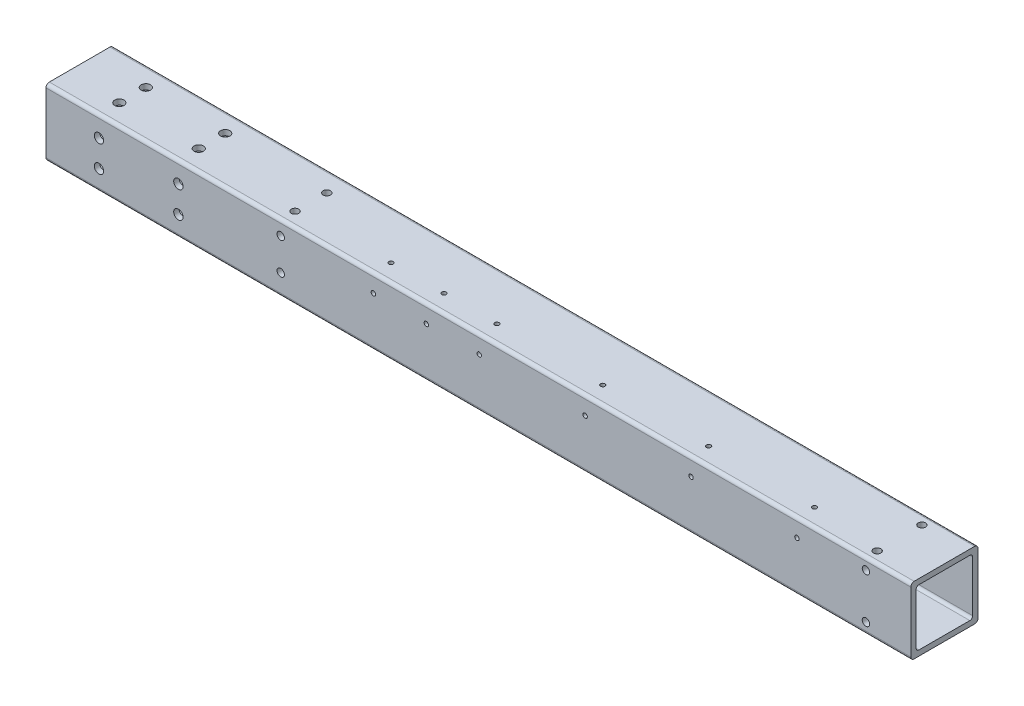
SolidWorks part; units mm, degrees
material "ASTM A36 Steel"
ref_plane "Front" through (0, 0, 0) normal (0, 0, 1) x (1, 0, 0)
ref_plane "Top" through (0, 0, 0) normal (0, 1, 0) x (1, 0, 0)
ref_plane "Right" through (0, 0, 0) normal (1, 0, 0) x (0, 0, -1)
sketch "Sketch1" plane through (0, 0, 0) normal (1, 0, 0) x (0, 0, -1)
  line L0 (-16.002, 0) -> (-19.05, 0) construction
  line L1 (17.145, -19.05) -> (-17.145, -19.05) construction
  line L2 (19.05, -17.145) -> (19.05, 17.145) construction
  line L3 (17.145, 19.05) -> (-17.145, 19.05) construction
  line L4 (-19.05, -17.145) -> (-19.05, 17.145) construction
  line L5 (19.05, -19.05) -> (-19.05, 19.05) construction
  line L6 (19.05, 19.05) -> (-19.05, -19.05) construction
  line L7 (14.4018, 16.002) -> (-14.4018, 16.002) construction
  line L8 (16.002, 14.4018) -> (16.002, -14.4018) construction
  line L9 (14.4018, -16.002) -> (-14.4018, -16.002) construction
  line L10 (-16.002, 14.4018) -> (-16.002, -14.4018) construction
  line L11 (16.002, 16.002) -> (-16.002, -16.002) construction
  line L12 (16.002, -16.002) -> (-16.002, 16.002) construction
  line L13 (0, -16.002) -> (0, -19.05) construction
  line L14 (16.002, -14.4018) -> (16.002, -19.05) construction
  line L15 (16.002, 0) -> (19.05, 0) construction
  line L16 (16.002, -19.05) -> (19.05, -19.05) construction
  arc A0 (-14.4018, -16.002) -> (-16.002, -14.4018) centre (-14.4018, -14.4018) cw construction
  arc A1 (16.002, -14.4018) -> (14.4018, -16.002) centre (14.4018, -14.4018) cw construction
  arc A2 (14.4018, 16.002) -> (16.002, 14.4018) centre (14.4018, 14.4018) cw construction
  arc A3 (-14.4018, 16.002) -> (-16.002, 14.4018) centre (-14.4018, 14.4018) ccw construction
  arc A4 (17.145, -19.05) -> (19.05, -17.145) centre (17.145, -17.145) ccw construction
  arc A5 (19.05, 17.145) -> (17.145, 19.05) centre (17.145, 17.145) ccw construction
  arc A6 (-17.145, 19.05) -> (-19.05, 17.145) centre (-17.145, 17.145) ccw construction
  arc A7 (-17.145, -19.05) -> (-19.05, -17.145) centre (-17.145, -17.145) cw construction
  point P0 (0, 0)
  point P6 (0, 0)
  dimension "D2" = 1.6002
  dimension "D3" = 1.905
  dimension "Outside Width" = 38.1
  dimension "Ouside Height" = 38.1
  dimension "Inside Height" = 32.004
  dimension "Wall Thickness" = 3.048
sketch "Sketch2" plane through (0, 0, 0) normal (0, 0, 1) x (1, 0, 0)
  line L0 (-245, 0) -> (245, 0) construction
  point P3 (-209.948, 0)
  point P4 (209.948, 0)
  dimension "Length" = 490
  dimension "D1" = 35.052
  dimension "D2" = 35.052
sketch "Sketch4" plane through (0, 0, 0) normal (1, 0, 0) x (0, 0, -1)
  line L8 (19.05, -17.145) -> (19.05, 17.145)
  line L9 (17.145, 19.05) -> (-17.145, 19.05)
  line L10 (-19.05, -17.145) -> (-19.05, 17.145)
  line L11 (17.145, -19.05) -> (-17.145, -19.05)
  line L12 (16.002, 14.4018) -> (16.002, -14.4018)
  line L13 (14.4018, -16.002) -> (-14.4018, -16.002)
  line L14 (-16.002, 14.4018) -> (-16.002, -14.4018)
  line L15 (14.4018, 16.002) -> (-14.4018, 16.002)
  arc A8 (19.05, 17.145) -> (17.145, 19.05) centre (17.145, 17.145) ccw
  arc A9 (-17.145, 19.05) -> (-19.05, 17.145) centre (-17.145, 17.145) ccw
  arc A10 (-19.05, -17.145) -> (-17.145, -19.05) centre (-17.145, -17.145) ccw
  arc A11 (17.145, -19.05) -> (19.05, -17.145) centre (17.145, -17.145) ccw
  arc A12 (14.4018, -16.002) -> (16.002, -14.4018) centre (14.4018, -14.4018) ccw
  arc A13 (-16.002, -14.4018) -> (-14.4018, -16.002) centre (-14.4018, -14.4018) ccw
  arc A14 (-14.4018, 16.002) -> (-16.002, 14.4018) centre (-14.4018, 14.4018) ccw
  arc A15 (16.002, 14.4018) -> (14.4018, 16.002) centre (14.4018, 14.4018) ccw
extrude "Boss-Extrude1" add sketch "Sketch4" along normal up to vertex (-245 mm away) and the other way up to vertex (-245 mm away) up to point (-245, 0, 0) other way up to point (245, 0, 0)
hole_wizard "Tap Drill for M5x0.8 Tap1" positions "Sketch5" profile "Sketch6" hole size "M5x0.8" standard "ANSI Metric" end condition up to next
sketch "Sketch5" plane through (0, 19.05, 0) normal (0, 1, 0) x (1, 0, 0)
  line L0 (-112, -10.95) -> (-112, 7.05) construction
  line L2 (-245, 17.145) -> (-245, -17.145) construction
  line L3 (245, 19.05) -> (-245, 19.05) construction
  point P0 (-112, 7.05)
  point P2 (-112, -10.95)
  point P20 (-112, -1.95)
  dimension "D1" = 18
  dimension "D2" = 133
  dimension "D3" = 21
sketch "Sketch6" plane through (-112, 19.05, -7.05) normal (1, 0, 0) x (0, 0, 1)
  line L0 (0, 0) -> (0, 3.048)
  line L1 (0, 3.048) -> (2.1, 3.048)
  line L2 (2.1, 3.048) -> (2.1, 0)
  line L5 (2.1, 0) -> (0, 0)
  line L11 (0, -6.35) -> (0, 107.95) construction
  dimension "Thru Hole Dia." = 4.2
  dimension "Thru Hole Depth" = 3.048
ref_plane "Plane1" through (0, 0, 0) normal (0, -0.7071, 0.7071) x (1, 0, 0)
hole_wizard "Tap Drill for M3x0.5 Tap1" positions "Sketch8" profile "Sketch9" hole size "M3x0.5" standard "ANSI Metric" end condition up to next
sketch "Sketch8" plane through (0, 0, 19.05) normal (0, 0, 1) x (1, 0, 0)
  line L0 (245, 17.145) -> (245, -17.145) construction
  line L1 (245, 19.05) -> (-245, 19.05) construction
  line L3 (-59.5, 9.05) -> (0.5, 9.05) construction
  point P0 (180.5, 9.05)
  point P5 (120.5, 9.05)
  point P6 (60.5, 9.05)
  point P7 (0.5, 9.05)
  point P8 (-59.5, 9.05)
  point P27 (-29.5, 9.05)
  dimension "D2" = 60
  dimension "D3" = 64.5
  dimension "D4" = 10
  dimension "D1" = 5
sketch "Sketch9" plane through (180.5, 9.05, 19.05) normal (1, 0, 0) x (0, -1, 0)
  line L0 (0, 0) -> (0, 3.048)
  line L1 (0, 3.048) -> (1.25, 3.048)
  line L2 (1.25, 3.048) -> (1.25, 0)
  line L5 (1.25, 0) -> (0, 0)
  line L11 (0, -6.35) -> (0, 107.95) construction
  dimension "Thru Hole Dia." = 2.5
  dimension "Thru Hole Depth" = 3.048
hole_wizard "Tap Drill for M5x0.8 Tap2" positions "Sketch21" profile "Sketch22" hole size "M5x0.8" standard "ANSI Metric"
sketch "Sketch21" plane through (0, 0, 19.05) normal (0, 0, 1) x (1, 0, 0)
  line L0 (219.6, 12.7) -> (219.6, -12.7) construction
  line L2 (245, 17.145) -> (245, -17.145) construction
  point P0 (219.6, 12.7)
  point P2 (219.6, -12.7)
  point P11 (245, 0)
  point P12 (219.6, 0)
  dimension "D1" = 25.4
  dimension "D2" = 25.4
sketch "Sketch22" plane through (219.6, 12.7, 19.05) normal (1, 0, 0) x (0, -1, 0)
  line L0 (0, 0) -> (0, 6.2618)
  line L1 (0, 6.2618) -> (2.1, 5)
  line L2 (2.1, 5) -> (2.1, 0)
  line L5 (2.1, 0) -> (0, 0)
  line L10 (0, 6.2618) -> (-2.1, 5) construction
  line L11 (0, -6.35) -> (0, 107.95) construction
  dimension "Hole Dia." = 4.2
  dimension "Hole Depth" = 5
  dimension "Drill Angle" = 118
mirror "Mirror1" about plane through (0, 0, 0) normal (0, -0.7071, 0.7071) of "Tap Drill for M5x0.8 Tap2", "Tap Drill for M5x0.8 Tap1", "Tap Drill for M3x0.5 Tap1"
ref_plane "Plane2" through (0, 0, 0) normal (0, 0.7071, 0.7071) x (1, 0, 0)
sketch "Sketch12" plane through (0, 19.05, 0) normal (0, 1, 0) x (1, 0, 0)
  line L0 (-215, -7.5) -> (-215, 7.5) construction
  line L1 (-245, 0) -> (-215, 0) construction
  line L4 (-245, 17.145) -> (-245, -17.145) construction
  dimension "D1" = 30
  dimension "D2" = 15
hole_wizard "M5 Clearance Hole1" positions "Sketch13" profile "Sketch15" hole size "M5" standard "ANSI Metric" end condition up to next
sketch "Sketch13" plane through (0, 19.05, 0) normal (0, 1, 0) x (1, 0, 0)
  point P0 (-215, 7.5)
  point P3 (-215, -7.5)
  point P6 (-170, -7.5)
  point P8 (-170, 7.5)
  dimension "D1" = 45
sketch "Sketch15" plane through (-215, 19.05, -7.5) normal (1, 0, 0) x (0, 0, 1)
  line L0 (0, 0) -> (0, 3.048)
  line L1 (0, 3.048) -> (2.65, 3.048)
  line L2 (2.65, 3.048) -> (2.65, 0)
  line L5 (2.65, 0) -> (0, 0)
  line L11 (0, -6.35) -> (0, 107.95) construction
  dimension "Thru Hole Dia." = 5.3
  dimension "Thru Hole Depth" = 3.048
hole_wizard "Tap Drill for M5x0.8 Tap3" positions "Sketch23" profile "Sketch24" hole size "M5x0.8" standard "ANSI Metric" end condition up to next
sketch "Sketch23" plane through (0, 0, -19.05) normal (0, 0, -1) x (-1, 0, 0)
  line L0 (-245, -19.05) -> (245, -19.05) construction
  line L2 (-245, -17.145) -> (-245, 17.145) construction
  point P0 (-250, -9.05)
  point P12 (-190, -9.05)
  point P13 (-130, -9.05)
  point P14 (-70, -9.05)
  point P15 (-10, -9.05)
  point P16 (50, -9.05)
  point P17 (110, -9.05)
  point P18 (170, -9.05)
  point P19 (230, -9.05)
  point P22 (-246.2165, -9.05)
  dimension "D1" = 10
  dimension "D2" = 5
  dimension "D4" = 60
  dimension "D3" = 9
sketch "Sketch24" plane through (250, -9.05, -19.05) normal (1, 0, 0) x (0, 1, 0)
  line L0 (0, 0) -> (0, 38.1)
  line L1 (0, 38.1) -> (2.1, 38.1)
  line L2 (2.1, 38.1) -> (2.1, 0)
  line L5 (2.1, 0) -> (0, 0)
  line L11 (0, -6.35) -> (0, 107.95) construction
  dimension "Thru Hole Dia." = 4.2
  dimension "Thru Hole Depth" = 38.1
mirror "Mirror2" about plane through (0, 0, 0) normal (0, -0.7071, 0.7071) of "Tap Drill for M5x0.8 Tap3", "M5 Clearance Hole1"
hole_wizard "Ø10.0 (10) Diameter Hole1" positions "Sketch17" profile "Sketch18" hole size "Ø10.0" standard "ANSI Metric" end condition up to next
sketch "Sketch17" plane through (0, 0, -16.002) normal (0, 0, 1) x (1, 0, 0)
  point P0 (-215, -7.5)
  point P3 (-215, 7.5)
  point P6 (-170, 7.5)
  point P9 (-170, -7.5)
sketch "Sketch18" plane through (-215, -7.5, -16.002) normal (1, 0, 0) x (0, -1, 0)
  line L0 (0, 0) -> (0, 3.048)
  line L1 (0, 3.048) -> (5, 3.048)
  line L2 (5, 3.048) -> (5, 0)
  line L5 (5, 0) -> (0, 0)
  line L11 (0, -6.35) -> (0, 107.95) construction
  dimension "Thru Hole Dia." = 10
  dimension "Thru Hole Depth" = 3.048
hole_wizard "Ø10.0 (10) Diameter Hole2" positions "Sketch19" profile "Sketch20" hole size "Ø10.0" standard "ANSI Metric" end condition up to next
sketch "Sketch19" plane through (0, -16.002, 0) normal (0, 1, 0) x (1, 0, 0)
  point P0 (-215, 7.5)
  point P3 (-215, -7.5)
  point P6 (-170, -7.5)
  point P9 (-170, 7.5)
sketch "Sketch20" plane through (-215, -16.002, -7.5) normal (1, 0, 0) x (0, 0, 1)
  line L0 (0, 0) -> (0, 3.048)
  line L1 (0, 3.048) -> (5, 3.048)
  line L2 (5, 3.048) -> (5, 0)
  line L5 (5, 0) -> (0, 0)
  line L11 (0, -6.35) -> (0, 107.95) construction
  dimension "Thru Hole Dia." = 10
  dimension "Thru Hole Depth" = 3.048
equation "\"D3@Sketch1\"=\"Outside Width@Sketch1\"*.05"
equation "\"D2@Sketch1\" = \"Inside Height@Sketch1\" * .05"
equation "\"D1@Sketch2\"=\"Outside Width@Sketch1\"-\"Wall Thickness@Sketch1\""
equation "\"D2@Sketch2\"=\"D1@Sketch2\""
